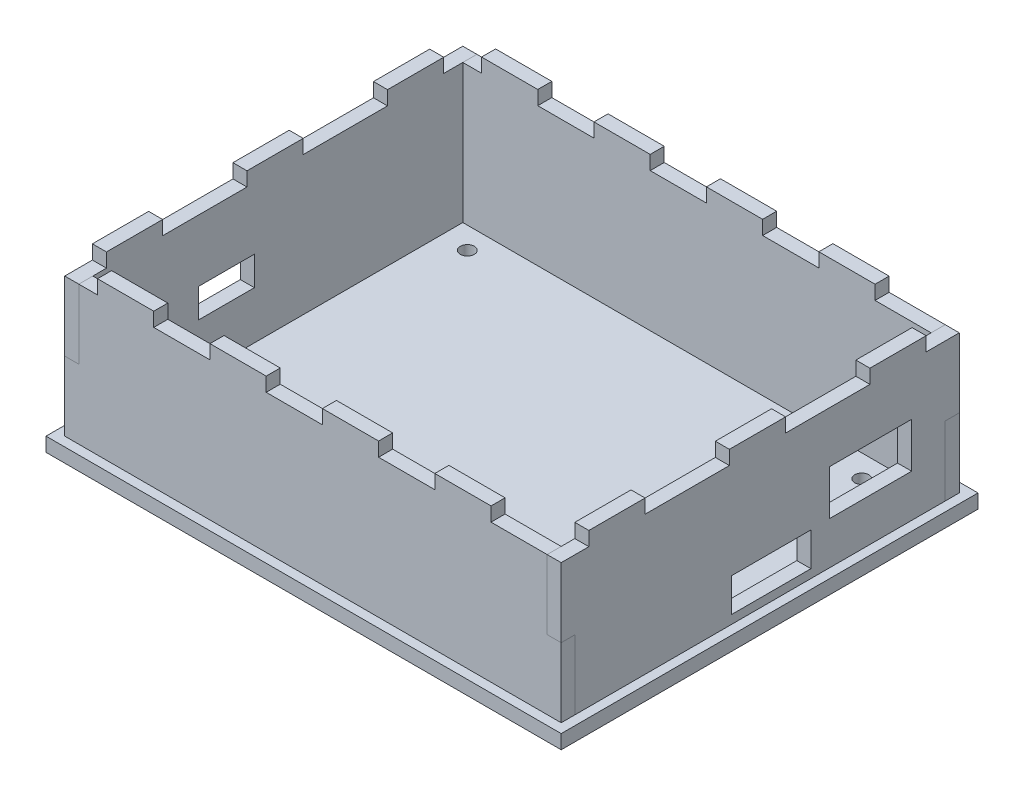
SolidWorks part; units mm, degrees
ref_plane "Front Plane" through (0, 0, 0) normal (0, 0, 1) x (1, 0, 0)
ref_plane "Top Plane" through (0, 0, 0) normal (0, 1, 0) x (1, 0, 0)
ref_plane "Right Plane" through (0, 0, 0) normal (1, 0, 0) x (0, 0, -1)
sketch "Sketch1" plane through (0, 0, 0) normal (0, 1, 0) x (1, 0, 0)
  line L0 (89.9441, -79.15) -> (89.9441, -4.1752) construction
  line L1 (-0.0307, -79.15) -> (89.9441, -79.15) construction
  line L2 (-0.0307, -4.1752) -> (-0.0307, -79.15) construction
  line L3 (89.9441, -4.1752) -> (-0.0307, -4.1752) construction
  line L13 (-0.0307, -41.6626) -> (36.6167, -41.6626) construction
  line L14 (-5.0307, -48.2445) -> (-2.0307, -48.2445)
  line L15 (-7.0307, 2.8248) -> (102.9441, 2.8248)
  line L16 (-7.0307, 2.8248) -> (-7.0307, -86.15)
  line L17 (-7.0307, -86.15) -> (102.9441, -86.15)
  line L18 (102.9441, 2.8248) -> (102.9441, -86.15)
  line L19 (-5.0307, -6.2445) -> (-2.0307, -6.2445)
  line L20 (-5.0307, -6.2445) -> (-5.0307, -18.2445)
  line L21 (-5.0307, -18.2445) -> (-2.0307, -18.2445)
  line L22 (-2.0307, -6.2445) -> (-2.0307, -18.2445)
  line L23 (-5.0307, -36.2445) -> (-5.0307, -48.2445)
  line L24 (-2.0307, -36.2445) -> (-2.0307, -48.2445)
  line L25 (-5.0307, -36.2445) -> (-2.0307, -36.2445)
  line L26 (-5.0307, -78.2445) -> (-2.0307, -78.2445)
  line L27 (-5.0307, -66.2445) -> (-5.0307, -78.2445)
  line L28 (-2.0307, -66.2445) -> (-2.0307, -78.2445)
  line L29 (-5.0307, -66.2445) -> (-2.0307, -66.2445)
  line L30 (47.9567, 2.8248) -> (47.9567, -53.2578) construction
  line L31 (100.9441, -66.2445) -> (97.9441, -66.2445)
  line L32 (97.9441, -66.2445) -> (97.9441, -78.2445)
  line L33 (100.9441, -66.2445) -> (100.9441, -78.2445)
  line L34 (100.9441, -78.2445) -> (97.9441, -78.2445)
  line L35 (100.9441, -36.2445) -> (97.9441, -36.2445)
  line L36 (97.9441, -36.2445) -> (97.9441, -48.2445)
  line L37 (100.9441, -36.2445) -> (100.9441, -48.2445)
  line L38 (97.9441, -6.2445) -> (97.9441, -18.2445)
  line L39 (100.9441, -18.2445) -> (97.9441, -18.2445)
  line L40 (100.9441, -6.2445) -> (100.9441, -18.2445)
  line L41 (100.9441, -6.2445) -> (97.9441, -6.2445)
  line L42 (100.9441, -48.2445) -> (97.9441, -48.2445)
  line L43 (1.9693, -2.1752) -> (1.9693, 0.8248)
  line L44 (1.9693, -2.1752) -> (13.9693, -2.1752)
  line L45 (13.9693, -2.1752) -> (13.9693, 0.8248)
  line L46 (1.9693, 0.8248) -> (13.9693, 0.8248)
  line L47 (25.9693, -2.1752) -> (25.9693, 0.8248)
  line L48 (25.9693, -2.1752) -> (37.9693, -2.1752)
  line L49 (25.9693, 0.8248) -> (37.9693, 0.8248)
  line L50 (37.9693, -2.1752) -> (37.9693, 0.8248)
  line L51 (49.9693, -2.1752) -> (49.9693, 0.8248)
  line L52 (49.9693, -2.1752) -> (61.9693, -2.1752)
  line L53 (49.9693, 0.8248) -> (61.9693, 0.8248)
  line L54 (61.9693, -2.1752) -> (61.9693, 0.8248)
  line L55 (73.9693, -2.1752) -> (73.9693, 0.8248)
  line L56 (73.9693, -2.1752) -> (85.9693, -2.1752)
  line L57 (73.9693, 0.8248) -> (85.9693, 0.8248)
  line L58 (85.9693, -2.1752) -> (85.9693, 0.8248)
  line L59 (47.9567, -86.15) -> (47.9567, -30.0674) construction
  line L60 (85.9693, -81.15) -> (85.9693, -84.15)
  line L61 (73.9693, -84.15) -> (85.9693, -84.15)
  line L62 (73.9693, -81.15) -> (85.9693, -81.15)
  line L63 (73.9693, -81.15) -> (73.9693, -84.15)
  line L64 (61.9693, -81.15) -> (61.9693, -84.15)
  line L65 (49.9693, -84.15) -> (61.9693, -84.15)
  line L66 (49.9693, -81.15) -> (61.9693, -81.15)
  line L67 (49.9693, -81.15) -> (49.9693, -84.15)
  line L68 (37.9693, -81.15) -> (37.9693, -84.15)
  line L69 (25.9693, -84.15) -> (37.9693, -84.15)
  line L70 (25.9693, -81.15) -> (37.9693, -81.15)
  line L71 (25.9693, -81.15) -> (25.9693, -84.15)
  line L72 (1.9693, -84.15) -> (13.9693, -84.15)
  line L73 (13.9693, -81.15) -> (13.9693, -84.15)
  line L74 (1.9693, -81.15) -> (13.9693, -81.15)
  line L75 (1.9693, -81.15) -> (1.9693, -84.15)
  circle A1 centre (2.5806, -76.4957) radius 1.5 construction
  circle A2 centre (2.8346, -6.8996) radius 1.5 construction
  arc A3 (3.2097, -4.1752) -> (2.4596, -4.1752) centre (2.8346, -6.8996) ccw construction
  circle A4 centre (87.1741, -6.9566) radius 1.5 construction
  circle A5 centre (87.9088, -6.9566) radius 1.5
  circle A6 centre (3.5806, -6.8296) radius 1.5
  circle A7 centre (3.8346, -76.4257) radius 1.5
  dimension "D5" = 5.5
  dimension "D1" = 7
  dimension "D2" = 7
  dimension "D3" = 13
  dimension "D4" = 7
  dimension "D6" = 3
  dimension "D7" = 2
  dimension "D8" = 12
  dimension "D9" = 3
  dimension "D10" = 12
  dimension "D11" = 2
  dimension "D12" = 3
  dimension "D13" = 9
  dimension "D14" = 4
extrude "Boss-Extrude7" add sketch "Sketch1" along normal blind 3
extrude "Boss-Extrude8" add sketch "Sketch1<9>" along normal blind 32.6 separate body contours L43 L46 L45 L44 | L47 L49 L50 L48 | L51 L53 L54 L52 | L55 L57 L58 L56 | L73 L72 L75 L74 | L71 L69 L68 L70 | L67 L65 L64 L66 | L63 L61 L60 L62
sketch "Sketch1<9>" plane through (0, 0, 0) normal (0, 1, 0) x (1, 0, 0) same geometry as "Sketch1"
sketch "Sketch11" plane through (0, 32.6, 0) normal (0, 1, 0) x (1, 0, 0)
  line L1 (-2.0307, -2.1752) -> (97.9441, -2.1752)
  line L2 (-2.0307, -2.1752) -> (-2.0307, 0.8248)
  line L3 (-2.0307, 0.8248) -> (97.9441, 0.8248)
  line L4 (97.9441, -2.1752) -> (97.9441, 0.8248)
  line L6 (-2.0307, -18.2445) -> (-2.0307, -6.2445) construction
  point P10 (0, 0)
  dimension "D1" = 0
extrude "Boss-Extrude10" add sketch "Sketch11" against normal blind 29.6
sketch "Sketch13" plane through (97.9441, 0, 0) normal (1, 0, 0) x (0, 0, -1)
  line L0 (0.8248, 3) -> (0.8248, 32.6) construction
  line L1 (-2.1752, 3) -> (0.8248, 3)
  line L2 (-2.1752, 3) -> (-2.1752, 17.8)
  line L3 (-2.1752, 17.8) -> (0.8248, 17.8)
  line L4 (0.8248, 3) -> (0.8248, 17.8)
  dimension "D1" = 14.8
extrude "Boss-Extrude11" add sketch "Sketch13" along normal blind 3
sketch "Sketch14" plane through (-2.0307, 0, 0) normal (-1, 0, 0) x (0, 0, 1)
  line L5 (2.1752, 3) -> (2.1752, 32.6) construction
  line L6 (-0.8248, 3) -> (2.1752, 3)
  line L7 (-0.8248, 3) -> (-0.8248, 17.8)
  line L8 (-0.8248, 17.8) -> (2.1752, 17.8)
  line L9 (2.1752, 3) -> (2.1752, 17.8)
  dimension "D1" = 14.8
extrude "Boss-Extrude12" add sketch "Sketch14" along normal blind 3
ref_plane "Plane5" through (0, 0, 41.6626) normal (0, 0, 1) x (1, 0, 0)
sketch "Sketch19" plane through (0, 32.6, 0) normal (0, 1, 0) x (1, 0, 0)
  line L0 (73.9693, 0.8248) -> (85.9693, 0.8248) construction
  line L1 (73.9693, -2.1752) -> (73.9693, 0.8248) construction
  line L2 (73.9693, -2.1752) -> (85.9693, -2.1752) construction
  line L3 (85.9693, -2.1752) -> (85.9693, 0.8248) construction
  line L4 (61.9693, -2.1752) -> (61.9693, 0.8248) construction
  line L5 (49.9693, 0.8248) -> (61.9693, 0.8248) construction
  line L6 (49.9693, -2.1752) -> (49.9693, 0.8248) construction
  line L7 (49.9693, -2.1752) -> (61.9693, -2.1752) construction
  line L8 (37.9693, -2.1752) -> (37.9693, 0.8248) construction
  line L9 (25.9693, 0.8248) -> (37.9693, 0.8248) construction
  line L10 (25.9693, -2.1752) -> (25.9693, 0.8248) construction
  line L11 (25.9693, -2.1752) -> (37.9693, -2.1752) construction
  line L12 (1.9693, -2.1752) -> (1.9693, 0.8248) construction
  line L13 (1.9693, 0.8248) -> (13.9693, 0.8248) construction
  line L14 (13.9693, -2.1752) -> (13.9693, 0.8248) construction
  line L15 (1.9693, -2.1752) -> (13.9693, -2.1752) construction
  line L16 (73.9693, 0.8248) -> (85.9693, 0.8248)
  line L17 (73.9693, -2.1752) -> (73.9693, 0.8248)
  line L18 (73.9693, -2.1752) -> (85.9693, -2.1752)
  line L19 (85.9693, -2.1752) -> (85.9693, 0.8248)
  line L20 (61.9693, -2.1752) -> (61.9693, 0.8248)
  line L21 (49.9693, 0.8248) -> (61.9693, 0.8248)
  line L22 (49.9693, -2.1752) -> (49.9693, 0.8248)
  line L23 (49.9693, -2.1752) -> (61.9693, -2.1752)
  line L24 (37.9693, -2.1752) -> (37.9693, 0.8248)
  line L25 (25.9693, 0.8248) -> (37.9693, 0.8248)
  line L26 (25.9693, -2.1752) -> (25.9693, 0.8248)
  line L27 (25.9693, -2.1752) -> (37.9693, -2.1752)
  line L28 (1.9693, -2.1752) -> (1.9693, 0.8248)
  line L29 (1.9693, 0.8248) -> (13.9693, 0.8248)
  line L30 (13.9693, -2.1752) -> (13.9693, 0.8248)
  line L31 (1.9693, -2.1752) -> (13.9693, -2.1752)
extrude "Boss-Extrude17" add sketch "Sketch19" along normal blind 3
delete or keep bodies "Body-Delete/Keep 1" type delete bodies bodies 115
delete or keep bodies "Body-Delete/Keep 2" type delete bodies bodies 116
delete or keep bodies "Body-Delete/Keep 3" type delete bodies bodies 117
delete or keep bodies "Body-Delete/Keep 4" type delete bodies bodies 118
extrude "Boss-Extrude18" add sketch "Sketch1<10>" along normal blind 32.6 separate body contours L42 L37 L35 L36 | L34 L33 L31 L32 | L39 L38 L41 L40 region at (99.4441, 0, 72.2445) region at (99.4441, 0, 42.2445)
sketch "Sketch1<10>" plane through (0, 0, 0) normal (0, 1, 0) x (1, 0, 0) same geometry as "Sketch1"
sketch "Sketch23" plane through (0, 3, 0) normal (0, 1, 0) x (1, 0, 0)
  line L0 (100.9441, -6.2445) -> (100.9441, -18.2445) construction
  line L1 (97.9441, -2.1752) -> (100.9441, -2.1752)
  line L2 (97.9441, -2.1752) -> (97.9441, -81.15)
  line L3 (97.9441, -81.15) -> (100.9441, -81.15)
  line L4 (100.9441, -2.1752) -> (100.9441, -81.15)
  line L5 (73.9693, -81.15) -> (85.9693, -81.15) construction
extrude "Boss-Extrude22" add sketch "Sketch23" along normal blind 29.6
sketch "Sketch24" plane through (0, 0, 2.1752) normal (0, 0, -1) x (-1, 0, 0)
  line L0 (-97.9441, 32.6) -> (-97.9441, 3) construction
  line L1 (-100.9441, 32.6) -> (-97.9441, 32.6)
  line L2 (-100.9441, 32.6) -> (-100.9441, 17.8)
  line L3 (-100.9441, 17.8) -> (-97.9441, 17.8)
  line L4 (-97.9441, 32.6) -> (-97.9441, 17.8)
extrude "Boss-Extrude23" add sketch "Sketch24" along normal blind 3
sketch "Sketch25" plane through (0, 0, 81.15) normal (0, 0, 1) x (1, 0, 0)
  line L0 (100.9441, 32.6) -> (100.9441, 3) construction
  line L1 (97.9441, 32.6) -> (100.9441, 32.6)
  line L2 (97.9441, 32.6) -> (97.9441, 17.8)
  line L3 (97.9441, 17.8) -> (100.9441, 17.8)
  line L4 (100.9441, 32.6) -> (100.9441, 17.8)
extrude "Boss-Extrude24" add sketch "Sketch25" along normal blind 3
sketch "Sketch26" plane through (0, 32.6, 0) normal (0, 1, 0) x (1, 0, 0)
  line L0 (100.9441, -78.2445) -> (97.9441, -78.2445) construction
  line L1 (97.9441, -66.2445) -> (97.9441, -78.2445) construction
  line L2 (100.9441, -66.2445) -> (100.9441, -78.2445) construction
  line L3 (100.9441, -66.2445) -> (97.9441, -66.2445) construction
  line L4 (100.9441, -48.2445) -> (97.9441, -48.2445) construction
  line L5 (97.9441, -36.2445) -> (97.9441, -48.2445) construction
  line L6 (100.9441, -36.2445) -> (100.9441, -48.2445) construction
  line L7 (100.9441, -36.2445) -> (97.9441, -36.2445) construction
  line L8 (100.9441, -6.2445) -> (97.9441, -6.2445) construction
  line L9 (100.9441, -6.2445) -> (100.9441, -18.2445) construction
  line L10 (100.9441, -18.2445) -> (97.9441, -18.2445) construction
  line L11 (97.9441, -6.2445) -> (97.9441, -18.2445) construction
  line L12 (100.9441, -78.2445) -> (97.9441, -78.2445)
  line L13 (97.9441, -66.2445) -> (97.9441, -78.2445)
  line L14 (100.9441, -66.2445) -> (100.9441, -78.2445)
  line L15 (100.9441, -66.2445) -> (97.9441, -66.2445)
  line L16 (100.9441, -48.2445) -> (97.9441, -48.2445)
  line L17 (97.9441, -36.2445) -> (97.9441, -48.2445)
  line L18 (100.9441, -36.2445) -> (100.9441, -48.2445)
  line L19 (100.9441, -36.2445) -> (97.9441, -36.2445)
  line L20 (100.9441, -6.2445) -> (97.9441, -6.2445)
  line L21 (100.9441, -6.2445) -> (100.9441, -18.2445)
  line L22 (100.9441, -18.2445) -> (97.9441, -18.2445)
  line L23 (97.9441, -6.2445) -> (97.9441, -18.2445)
extrude "Boss-Extrude25" add sketch "Sketch26" along normal blind 3
ref_plane "Plane6" through (47.9567, 0, 0) normal (-1, 0, 0) x (0, 0, 1)
mirror "Mirror4" about plane through (47.9567, 0, 0) normal (-1, 0, 0) of bodies 137
mirror "Mirror5" about plane through (0, 0, 41.6626) normal (0, 0, 1) of bodies 130
sketch "Sketch28" plane through (100.9441, 0, 0) normal (1, 0, 0) x (0, 0, -1)
  line L32 (-36.2445, 3) -> (-18.2445, 3)
  line L33 (-18.2445, 3) -> (-18.2445, 0)
  line L34 (-18.2445, 0) -> (-6.2445, 0)
  line L35 (-6.2445, 0) -> (-6.2445, 3)
  line L36 (-6.2445, 3) -> (-2.1752, 3)
  line L37 (-2.1752, 3) -> (-2.1752, 17.8)
  line L38 (-2.1752, 17.8) -> (0.8248, 17.8)
  line L39 (0.8248, 17.8) -> (0.8248, 32.6)
  line L40 (0.8248, 32.6) -> (-6.2445, 32.6)
  line L41 (-6.2445, 32.6) -> (-6.2445, 35.6)
  line L42 (-6.2445, 35.6) -> (-18.2445, 35.6)
  line L43 (-18.2445, 35.6) -> (-18.2445, 32.6)
  line L44 (-18.2445, 32.6) -> (-36.2445, 32.6)
  line L45 (-36.2445, 32.6) -> (-36.2445, 35.6)
  line L46 (-36.2445, 35.6) -> (-48.2445, 35.6)
  line L47 (-48.2445, 35.6) -> (-48.2445, 32.6)
  line L48 (-48.2445, 32.6) -> (-66.2445, 32.6)
  line L49 (-66.2445, 32.6) -> (-66.2445, 35.6)
  line L50 (-66.2445, 35.6) -> (-78.2445, 35.6)
  line L51 (-78.2445, 35.6) -> (-78.2445, 32.6)
  line L52 (-78.2445, 32.6) -> (-84.15, 32.6)
  line L53 (-84.15, 32.6) -> (-84.15, 17.8)
  line L54 (-84.15, 17.8) -> (-81.15, 17.8)
  line L55 (-81.15, 17.8) -> (-81.15, 3)
  line L56 (-81.15, 3) -> (-78.2445, 3)
  line L57 (-78.2445, 3) -> (-78.2445, 0)
  line L58 (-78.2445, 0) -> (-66.2445, 0)
  line L59 (-66.2445, 0) -> (-66.2445, 3)
  line L60 (-66.2445, 3) -> (-48.2445, 3)
  line L61 (-48.2445, 3) -> (-48.2445, 0)
  line L62 (-48.2445, 0) -> (-36.2445, 0)
  line L63 (-36.2445, 0) -> (-36.2445, 3)
  line L64 (-36.2445, 3) -> (-18.2445, 3)
  line L65 (-18.2445, 3) -> (-18.2445, 0)
  line L66 (-18.2445, 0) -> (-6.2445, 0)
  line L67 (-6.2445, 0) -> (-6.2445, 3)
  line L68 (-6.2445, 3) -> (-2.1752, 3)
  line L69 (-2.1752, 3) -> (-2.1752, 17.8)
  line L70 (-2.1752, 17.8) -> (0.8248, 17.8)
  line L71 (0.8248, 17.8) -> (0.8248, 32.6)
  line L72 (0.8248, 32.6) -> (-6.2445, 32.6)
  line L73 (-6.2445, 32.6) -> (-6.2445, 35.6)
  line L74 (-6.2445, 35.6) -> (-18.2445, 35.6)
  line L75 (-18.2445, 35.6) -> (-18.2445, 32.6)
  line L76 (-18.2445, 32.6) -> (-36.2445, 32.6)
  line L77 (-36.2445, 32.6) -> (-36.2445, 35.6)
  line L78 (-36.2445, 35.6) -> (-48.2445, 35.6)
  line L79 (-48.2445, 35.6) -> (-48.2445, 32.6)
  line L80 (-48.2445, 32.6) -> (-66.2445, 32.6)
  line L81 (-66.2445, 32.6) -> (-66.2445, 35.6)
  line L82 (-66.2445, 35.6) -> (-78.2445, 35.6)
  line L83 (-78.2445, 35.6) -> (-78.2445, 32.6)
  line L84 (-78.2445, 32.6) -> (-84.15, 32.6)
  line L85 (-84.15, 32.6) -> (-84.15, 17.8)
  line L86 (-84.15, 17.8) -> (-81.15, 17.8)
  line L87 (-81.15, 17.8) -> (-81.15, 3)
  line L88 (-81.15, 3) -> (-78.2445, 3)
  line L89 (-78.2445, 3) -> (-78.2445, 0)
  line L90 (-78.2445, 0) -> (-66.2445, 0)
  line L91 (-66.2445, 0) -> (-66.2445, 3)
  line L92 (-66.2445, 3) -> (-48.2445, 3)
  line L93 (-48.2445, 3) -> (-48.2445, 0)
  line L94 (-48.2445, 0) -> (-36.2445, 0)
  line L95 (-36.2445, 0) -> (-36.2445, 3)
  dimension "D1" = 0
sketch "Sketch29" plane through (100.9441, 0, 0) normal (1, 0, 0) x (0, 0, -1)
  line L0 (-46.2466, 11.0297) -> (-46.2466, 5.8297) construction
  line L1 (-47.7466, 4.8297) -> (-30.8466, 4.8297)
  line L2 (-47.7466, 4.8297) -> (-47.7466, 12)
  line L3 (-47.7466, 12) -> (-30.8466, 12)
  line L4 (-30.8466, 4.8297) -> (-30.8466, 12)
  line L5 (-4.1752, 11) -> (-79.15, 11) construction
  line L6 (-46.2466, 5.8297) -> (-32.3466, 5.8297) construction
  line L7 (-32.3466, 5.8297) -> (-32.3466, 11.0297) construction
  line L8 (-25.8394, 12.6001) -> (-25.8394, 19.9001) construction
  line L9 (-26.8394, 12.1001) -> (-9.3394, 12.1001)
  line L10 (-26.8394, 12.1001) -> (-26.8394, 21.7001)
  line L11 (-26.8394, 21.7001) -> (-9.3394, 21.7001)
  line L12 (-9.3394, 12.1001) -> (-9.3394, 21.7001)
  line L13 (-25.0394, 20.7001) -> (-11.1394, 20.7001) construction
  line L14 (-10.3394, 19.9001) -> (-10.3394, 12.6001) construction
  line L15 (-79.15, 12.6001) -> (-4.1752, 12.6001) construction
  dimension "D1" = 1.5
  dimension "D2" = 1
  dimension "D3" = 1
  dimension "D4" = 1.5
  dimension "D5" = 1
  dimension "D6" = 1
  dimension "D7" = 1
  dimension "D8" = 0.5
extrude "Cut-Extrude4" cut sketch "Sketch29" against normal blind 10 contours L4 L3 L2 L1 | L11 L12 L9 L10
sketch "Sketch30" plane through (-5.0307, 0, 0) normal (-1, 0, 0) x (0, 0, 1)
  line L0 (57.1053, 16.3999) -> (57.1053, 15.2) construction
  line L1 (58.6053, 19.3998) -> (46.6659, 19.3998)
  line L2 (58.6053, 19.3998) -> (58.6053, 13.2)
  line L3 (58.6053, 13.2) -> (46.6659, 13.2)
  line L4 (46.6659, 19.3998) -> (46.6659, 13.2)
  line L5 (48.1659, 15.2) -> (48.1659, 16.3999) construction
  line L6 (49.1659, 17.3998) -> (56.1053, 17.3998) construction
  line L7 (62.1356, 14.2) -> (43.1356, 14.2) construction
  dimension "D1" = 1.5
  dimension "D2" = 1.5
  dimension "D3" = 2
  dimension "D4" = 1
extrude "Cut-Extrude5" cut sketch "Sketch30" against normal blind 10
